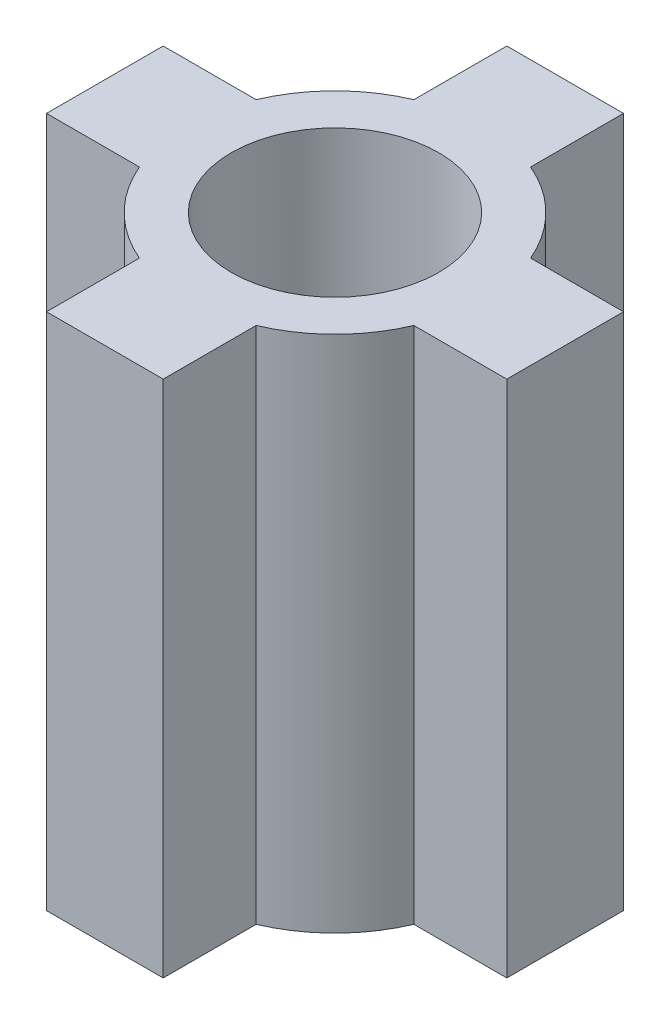
SolidWorks part; units mm, degrees
ref_plane "Front Plane" through (0, 0, 0) normal (0, 0, 1) x (1, 0, 0)
ref_plane "Top Plane" through (0, 0, 0) normal (0, 1, 0) x (1, 0, 0)
ref_plane "Right Plane" through (0, 0, 0) normal (1, 0, 0) x (0, 0, -1)
sketch "Sketch1" plane through (0, 0, 0) normal (0, 1, 0) x (1, 0, 0)
  circle A0 centre (0, 0) radius 2.3
  circle A1 centre (0, 0) radius 1.6
  dimension "D1" = 4.6
  dimension "D2" = 3.2
extrude "Boss-Extrude1" add sketch "Sketch1" along normal blind 8
sketch "Sketch2" plane through (0, 8, 0) normal (0, 1, 0) x (1, 0, 0)
  line L0 (0, 0) -> (-3.55, 0) construction
  line L1 (-3.55, -0.9) -> (-3.55, 0.9)
  line L2 (-3.55, 0.9) -> (-2.1166, 0.9)
  line L3 (-3.55, -0.9) -> (-2.1166, -0.9)
  circle A0 centre (0, 0) radius 2.3 construction
  arc A1 (-2.1166, -0.9) -> (-2.1166, 0.9) centre (0, 0) cw
  point P6 (-3.55, 0)
  dimension "D1" = 3.55
  dimension "D2" = 1.8
extrude "Boss-Extrude2" add sketch "Sketch2" against normal up to surface (8 mm away) up to face at (0, 0, 2.3)
pattern_circular "CirPattern1" count 4 over 360 about axis through (0, 8, 0) along (0, -1, 0) of "Boss-Extrude2"
sketch "Sketch3" plane through (0, 0, 0) normal (0, -1, 0) x (1, 0, 0)
  line L1 (-0.5568, -1.5) -> (0.5568, -1.5)
  circle A0 centre (0, 0) radius 1.6 construction
  arc A1 (0.5568, -1.5) -> (-0.5568, -1.5) centre (0, 0) cw
  point P7 (0, -1.5)
  dimension "D1" = 0.1
extrude "Boss-Extrude3" add sketch "Sketch3" against normal blind 1.25 contours L1 A1
fillet "Fillet1" radius 0.1 1 edges at (0, 1.25, -1.6)
